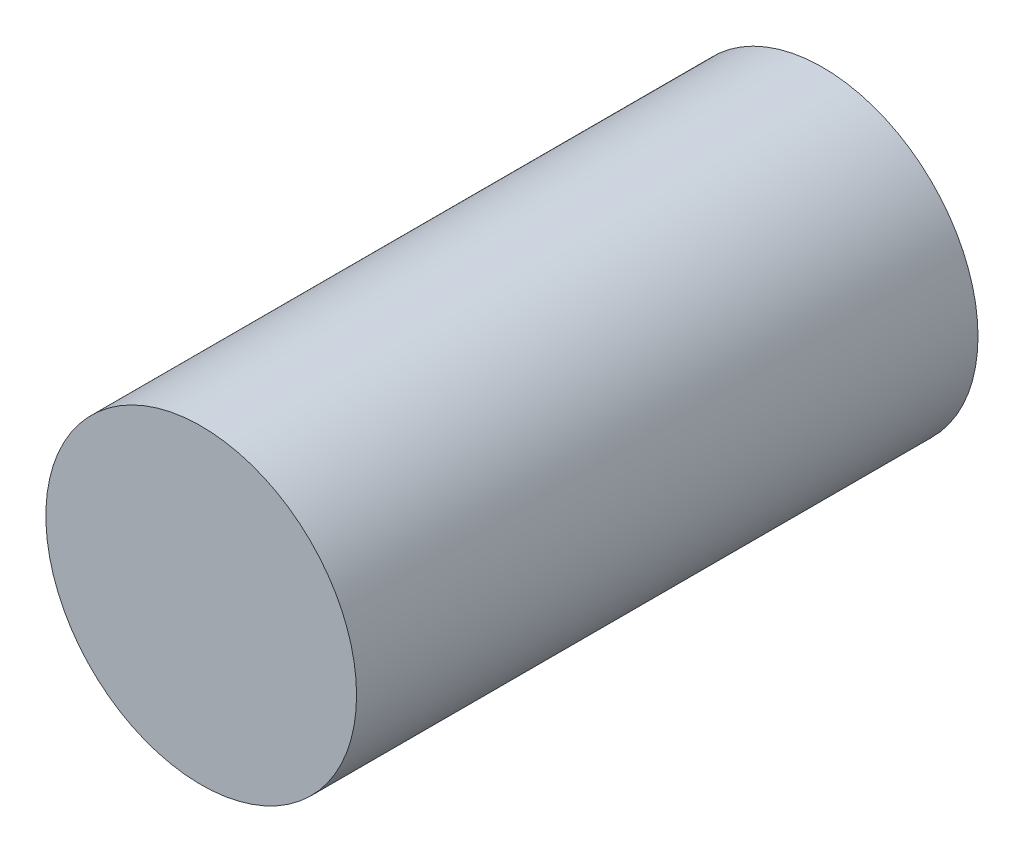
SolidWorks part; units mm, degrees
ref_plane "Front" through (0, 0, 0) normal (0, 0, 1) x (1, 0, 0)
ref_plane "Top" through (0, 0, 0) normal (0, 1, 0) x (1, 0, 0)
ref_plane "Right" through (0, 0, 0) normal (1, 0, 0) x (0, 0, -1)
sketch "Sketch1" plane through (0, 0, 0) normal (0, 0, 1) x (1, 0, 0)
  circle A0 centre (0, 0) radius 63.5
  dimension "D1" = 127
extrude "Extrude1" add sketch "Sketch1" along normal mid plane 254
ref_axis "Axis1" through (0, 0, 127) along (0, 0, -1)
